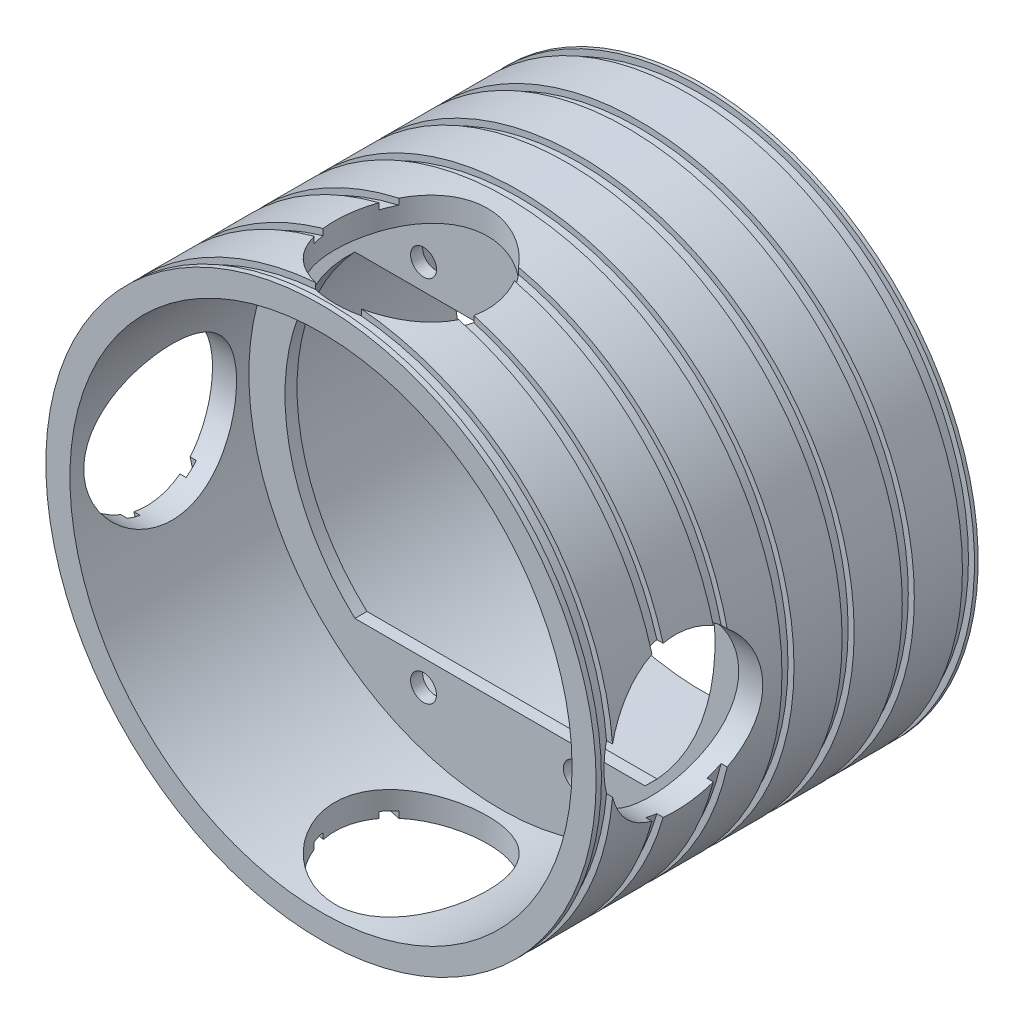
SolidWorks part; units mm, degrees
material "6061 Alloy"
ref_plane "Front Plane" through (0, 0, 0) normal (0, 0, 1) x (1, 0, 0)
ref_plane "Top Plane" through (0, 0, 0) normal (0, 1, 0) x (1, 0, 0)
ref_plane "Right Plane" through (0, 0, 0) normal (1, 0, 0) x (0, 0, -1)
sketch "Sketch1" plane through (0, 0, 0) normal (0, 0, 1) x (1, 0, 0)
  line L0 (0, -35.7344) -> (0, 35.7344) construction
  line L1 (-35.7344, 0) -> (35.7344, 0) construction
  line L2 (24.1131, -26.3724) -> (-24.1131, -26.3724)
  line L3 (24.1131, 26.3724) -> (-24.1131, 26.3724)
  circle A0 centre (0, 0) radius 41.7344
  circle A1 centre (0, 0) radius 45.7344
  circle A2 centre (0, 0) radius 35.7344
  arc A3 (37.225, 18.8696) -> (-37.225, 18.8696) centre (0, 0) ccw construction
  dimension "D1" = 6
  dimension "D2" = 4
extrude "Boss-Extrude1" add sketch "Sketch1" against normal up to surface (31.75 mm away) contours A1 A0 region at (-44.4409, 0, 0)
extrude "Boss-Extrude2" add sketch "Sketch1<3>" along normal blind 2 contours A0 A2 | L3 A2 | L2 A2 region at (0, -30.1627, 0) region at (0, 30.1627, 0) region at (-40.554, 0, 0)
sketch "Sketch1<3>" plane through (0, 0, 0) normal (0, 0, 1) x (1, 0, 0) same geometry as "Sketch1"
extrude "Boss-Extrude3" add sketch "Sketch1<4>" along normal blind 31.75 contours A1 A0 region at (-44.4409, 0, 0)
sketch "Sketch1<4>" plane through (0, 0, 0) normal (0, 0, 1) x (1, 0, 0) same geometry as "Sketch1"
ref_plane "Plane4" through (0, 0, 0) normal (1, 0, 0) x (0, 0, -1)
sketch "Sketch2" plane through (0, 0, 0) normal (1, 0, 0) x (0, 0, -1)
  line L1 (-18.8627, 44.7344) -> (-20.8627, 44.7344)
  line L2 (-18.8627, 44.7344) -> (-18.8627, 46.7344)
  line L3 (-18.8627, 46.7344) -> (-20.8627, 46.7344)
  line L4 (-20.8627, 44.7344) -> (-20.8627, 46.7344)
  line L5 (31.75, 45.7344) -> (-31.75, 45.7344) construction
  line L6 (-28.8627, 44.7344) -> (-30.8627, 44.7344)
  line L7 (-28.8627, 44.7344) -> (-28.8627, 46.7344)
  line L8 (-28.8627, 46.7344) -> (-30.8627, 46.7344)
  line L9 (-30.8627, 44.7344) -> (-30.8627, 46.7344)
  line L10 (-28.8627, 44.7344) -> (-30.8627, 46.7344) construction
  line L11 (-28.8627, 46.7344) -> (-30.8627, 44.7344) construction
  line L12 (-18.8627, 44.7344) -> (-20.8627, 46.7344) construction
  line L13 (-18.8627, 46.7344) -> (-20.8627, 44.7344) construction
  line L14 (-8.8627, 44.7344) -> (-10.8627, 44.7344)
  line L15 (-8.8627, 44.7344) -> (-8.8627, 46.7344)
  line L16 (-8.8627, 46.7344) -> (-10.8627, 46.7344)
  line L17 (-10.8627, 44.7344) -> (-10.8627, 46.7344)
  line L18 (-8.8627, 44.7344) -> (-10.8627, 46.7344) construction
  line L19 (-8.8627, 46.7344) -> (-10.8627, 44.7344) construction
  line L20 (1.1373, 44.7344) -> (-0.8627, 44.7344)
  line L21 (1.1373, 44.7344) -> (1.1373, 46.7344)
  line L22 (1.1373, 46.7344) -> (-0.8627, 46.7344)
  line L23 (-0.8627, 44.7344) -> (-0.8627, 46.7344)
  line L24 (1.1373, 44.7344) -> (-0.8627, 46.7344) construction
  line L25 (1.1373, 46.7344) -> (-0.8627, 44.7344) construction
  line L26 (11.1373, 44.7344) -> (9.1373, 44.7344)
  line L27 (11.1373, 44.7344) -> (11.1373, 46.7344)
  line L28 (11.1373, 46.7344) -> (9.1373, 46.7344)
  line L29 (9.1373, 44.7344) -> (9.1373, 46.7344)
  line L30 (11.1373, 44.7344) -> (9.1373, 46.7344) construction
  line L31 (11.1373, 46.7344) -> (9.1373, 44.7344) construction
  line L32 (21.1373, 44.7344) -> (19.1373, 44.7344)
  line L33 (21.1373, 44.7344) -> (21.1373, 46.7344)
  line L34 (21.1373, 46.7344) -> (19.1373, 46.7344)
  line L35 (19.1373, 44.7344) -> (19.1373, 46.7344)
  line L36 (21.1373, 44.7344) -> (19.1373, 46.7344) construction
  line L37 (21.1373, 46.7344) -> (19.1373, 44.7344) construction
  line L38 (31.1373, 44.7344) -> (29.1373, 44.7344)
  line L39 (31.1373, 44.7344) -> (31.1373, 46.7344)
  line L40 (31.1373, 46.7344) -> (29.1373, 46.7344)
  line L41 (29.1373, 44.7344) -> (29.1373, 46.7344)
  line L42 (31.1373, 44.7344) -> (29.1373, 46.7344) construction
  line L43 (31.1373, 46.7344) -> (29.1373, 44.7344) construction
  point P0 (-19.8627, 45.7344)
  point P8 (-9.8627, 45.7344)
  point P9 (-29.8627, 45.7344)
  point P18 (0.1373, 45.7344)
  point P23 (10.1373, 45.7344)
  point P28 (20.1373, 45.7344)
  point P33 (30.1373, 45.7344)
  dimension "D1" = 2
  dimension "D2" = 7
ref_axis "Axis1" through (0, 0, 2) along (0, 0, 1)
revolve "Cut-Revolve1" cut sketch "Sketch2" angle 360 about axis through (0, 0, 2) along (0, 0, 1)
sketch "Sketch7" plane through (0, 0, 0) normal (1, 0, 0) x (0, 0, -1)
  line L0 (-31.75, 0) -> (31.75, 0) construction
  line L1 (31.75, -45.7344) -> (31.75, 45.7344) construction
  line L2 (-31.75, 45.7344) -> (-31.75, -45.7344) construction
  circle A0 centre (-16.75, 0) radius 12.7
  dimension "D1" = 25.4
  dimension "D2" = 15
extrude "Cut-Extrude1" cut sketch "Sketch7" against normal through all both and the other way through all
sketch "Sketch8" plane through (0, 0, 0) normal (0, 1, 0) x (1, 0, 0)
  line L0 (0, -31.75) -> (0, 31.75) construction
  line L3 (-45.7344, -31.75) -> (45.7344, -31.75) construction
  line L4 (41.7344, 31.75) -> (-41.7344, 31.75) construction
  circle A0 centre (0, -16.75) radius 12.7
  dimension "D1" = 25.4
  dimension "D2" = 15
extrude "Cut-Extrude2" cut sketch "Sketch8" against normal through all both and the other way through all
hole_wizard "#8 Clearance Hole1" positions "Sketch9" profile "Sketch10" hole size "#8" standard "ANSI Inch" end condition through all
sketch "Sketch9" plane through (-9.4006, -2.5125, 0) normal (0, 0, -1) x (-1, 0, 0)
  point P0 (3.2994, 33.1344)
  point P1 (-22.1006, 33.1344)
  point P2 (-22.1006, -28.1094)
  point P3 (3.2994, -28.1094)
sketch "Sketch10" plane through (-12.7, 30.6219, 0) normal (1, 0, 0) x (0, 1, 0)
  line L0 (0, 0) -> (0, 31.75)
  line L1 (0, 31.75) -> (2.1526, 31.75)
  line L2 (2.1526, 31.75) -> (2.1526, 0)
  line L3 (2.1526, 0) -> (0, 0)
  line L4 (0, -6.35) -> (0, 107.95) construction
  dimension "Thru Hole Dia." = 4.3053
  dimension "Thru Hole Depth" = 31.75
fillet "Fillet1" radius 1 1 edges at (41.7344, 0, 0)
